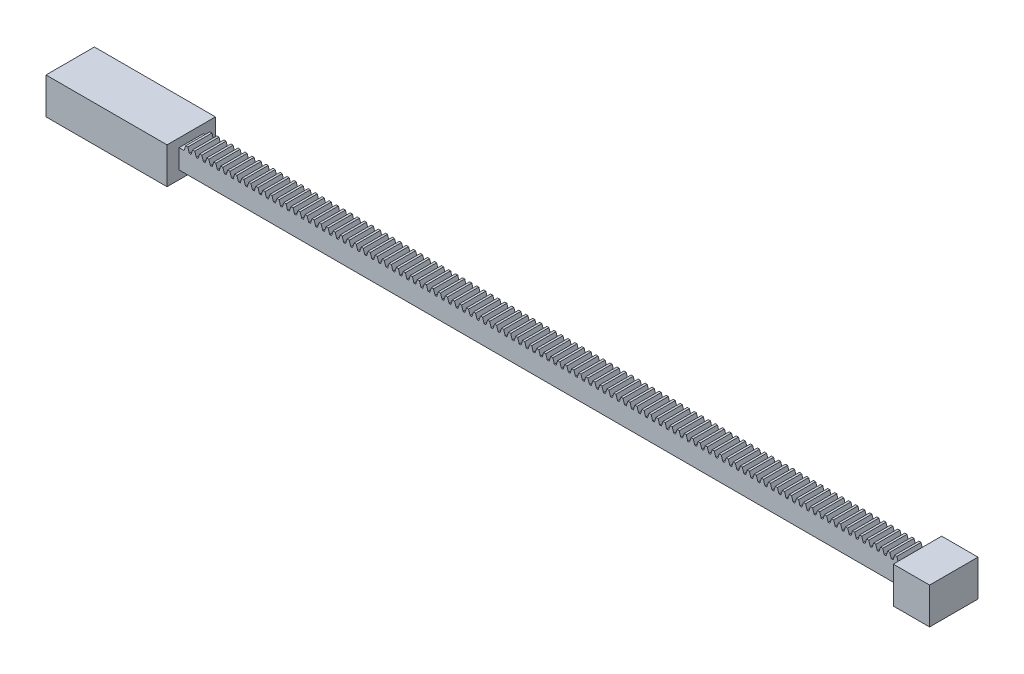
SolidWorks part; units mm, degrees
ref_plane "Front Plane" through (0, 0, 0) normal (0, 0, 1) x (1, 0, 0)
ref_plane "Top Plane" through (0, 0, 0) normal (0, 1, 0) x (1, 0, 0)
ref_plane "Right Plane" through (0, 0, 0) normal (1, 0, 0) x (0, 0, -1)
sketch "Sketch1" plane through (0, 0, 0) normal (0, 0, 1) x (1, 0, 0)
  line L0 (147.8394, 4) -> (148.4797, 6)
  line L1 (-150, 4) -> (150, 4)
  line L2 (-150, 4) -> (-150, -4)
  line L3 (-150, -4) -> (150, -4)
  line L4 (150, 4) -> (150, -4)
  line L5 (-150, 4) -> (150, -4) construction
  line L6 (-150, -4) -> (150, 4) construction
  line L7 (148.4797, 6) -> (149.3597, 6)
  line L8 (149.3597, 6) -> (150, 4)
  line L9 (144.9394, 4) -> (145.5797, 6)
  line L10 (145.5797, 6) -> (146.4597, 6)
  line L11 (146.4597, 6) -> (147.1, 4)
  line L12 (142.0394, 4) -> (142.6797, 6)
  line L13 (142.6797, 6) -> (143.5597, 6)
  line L14 (143.5597, 6) -> (144.2, 4)
  line L15 (139.1394, 4) -> (139.7797, 6)
  line L16 (139.7797, 6) -> (140.6597, 6)
  line L17 (140.6597, 6) -> (141.3, 4)
  line L18 (136.2394, 4) -> (136.8797, 6)
  line L19 (136.8797, 6) -> (137.7597, 6)
  line L20 (137.7597, 6) -> (138.4, 4)
  line L21 (133.3394, 4) -> (133.9797, 6)
  line L22 (133.9797, 6) -> (134.8597, 6)
  line L23 (134.8597, 6) -> (135.5, 4)
  line L24 (130.4394, 4) -> (131.0797, 6)
  line L25 (131.0797, 6) -> (131.9597, 6)
  line L26 (131.9597, 6) -> (132.6, 4)
  line L27 (127.5394, 4) -> (128.1797, 6)
  line L28 (128.1797, 6) -> (129.0597, 6)
  line L29 (129.0597, 6) -> (129.7, 4)
  line L30 (124.6394, 4) -> (125.2797, 6)
  line L31 (125.2797, 6) -> (126.1597, 6)
  line L32 (126.1597, 6) -> (126.8, 4)
  line L33 (121.7394, 4) -> (122.3797, 6)
  line L34 (122.3797, 6) -> (123.2597, 6)
  line L35 (123.2597, 6) -> (123.9, 4)
  line L36 (118.8394, 4) -> (119.4797, 6)
  line L37 (119.4797, 6) -> (120.3597, 6)
  line L38 (120.3597, 6) -> (121, 4)
  line L39 (115.9394, 4) -> (116.5797, 6)
  line L40 (116.5797, 6) -> (117.4597, 6)
  line L41 (117.4597, 6) -> (118.1, 4)
  line L42 (113.0394, 4) -> (113.6797, 6)
  line L43 (113.6797, 6) -> (114.5597, 6)
  line L44 (114.5597, 6) -> (115.2, 4)
  line L45 (110.1394, 4) -> (110.7797, 6)
  line L46 (110.7797, 6) -> (111.6597, 6)
  line L47 (111.6597, 6) -> (112.3, 4)
  line L48 (107.2394, 4) -> (107.8797, 6)
  line L49 (107.8797, 6) -> (108.7597, 6)
  line L50 (108.7597, 6) -> (109.4, 4)
  line L51 (104.3394, 4) -> (104.9797, 6)
  line L52 (104.9797, 6) -> (105.8597, 6)
  line L53 (105.8597, 6) -> (106.5, 4)
  line L54 (101.4394, 4) -> (102.0797, 6)
  line L55 (102.0797, 6) -> (102.9597, 6)
  line L56 (102.9597, 6) -> (103.6, 4)
  line L57 (98.5394, 4) -> (99.1797, 6)
  line L58 (99.1797, 6) -> (100.0597, 6)
  line L59 (100.0597, 6) -> (100.7, 4)
  line L60 (95.6394, 4) -> (96.2797, 6)
  line L61 (96.2797, 6) -> (97.1597, 6)
  line L62 (97.1597, 6) -> (97.8, 4)
  line L63 (92.7394, 4) -> (93.3797, 6)
  line L64 (93.3797, 6) -> (94.2597, 6)
  line L65 (94.2597, 6) -> (94.9, 4)
  line L66 (89.8394, 4) -> (90.4797, 6)
  line L67 (90.4797, 6) -> (91.3597, 6)
  line L68 (91.3597, 6) -> (92, 4)
  line L69 (86.9394, 4) -> (87.5797, 6)
  line L70 (87.5797, 6) -> (88.4597, 6)
  line L71 (88.4597, 6) -> (89.1, 4)
  line L72 (84.0394, 4) -> (84.6797, 6)
  line L73 (84.6797, 6) -> (85.5597, 6)
  line L74 (85.5597, 6) -> (86.2, 4)
  line L75 (81.1394, 4) -> (81.7797, 6)
  line L76 (81.7797, 6) -> (82.6597, 6)
  line L77 (82.6597, 6) -> (83.3, 4)
  line L78 (78.2394, 4) -> (78.8797, 6)
  line L79 (78.8797, 6) -> (79.7597, 6)
  line L80 (79.7597, 6) -> (80.4, 4)
  line L81 (75.3394, 4) -> (75.9797, 6)
  line L82 (75.9797, 6) -> (76.8597, 6)
  line L83 (76.8597, 6) -> (77.5, 4)
  line L84 (72.4394, 4) -> (73.0797, 6)
  line L85 (73.0797, 6) -> (73.9597, 6)
  line L86 (73.9597, 6) -> (74.6, 4)
  line L87 (69.5394, 4) -> (70.1797, 6)
  line L88 (70.1797, 6) -> (71.0597, 6)
  line L89 (71.0597, 6) -> (71.7, 4)
  line L90 (66.6394, 4) -> (67.2797, 6)
  line L91 (67.2797, 6) -> (68.1597, 6)
  line L92 (68.1597, 6) -> (68.8, 4)
  line L93 (63.7394, 4) -> (64.3797, 6)
  line L94 (64.3797, 6) -> (65.2597, 6)
  line L95 (65.2597, 6) -> (65.9, 4)
  line L96 (60.8394, 4) -> (61.4797, 6)
  line L97 (61.4797, 6) -> (62.3597, 6)
  line L98 (62.3597, 6) -> (63, 4)
  line L99 (57.9394, 4) -> (58.5797, 6)
  line L100 (58.5797, 6) -> (59.4597, 6)
  line L101 (59.4597, 6) -> (60.1, 4)
  line L102 (55.0394, 4) -> (55.6797, 6)
  line L103 (55.6797, 6) -> (56.5597, 6)
  line L104 (56.5597, 6) -> (57.2, 4)
  line L105 (52.1394, 4) -> (52.7797, 6)
  line L106 (52.7797, 6) -> (53.6597, 6)
  line L107 (53.6597, 6) -> (54.3, 4)
  line L108 (49.2394, 4) -> (49.8797, 6)
  line L109 (49.8797, 6) -> (50.7597, 6)
  line L110 (50.7597, 6) -> (51.4, 4)
  line L111 (46.3394, 4) -> (46.9797, 6)
  line L112 (46.9797, 6) -> (47.8597, 6)
  line L113 (47.8597, 6) -> (48.5, 4)
  line L114 (43.4394, 4) -> (44.0797, 6)
  line L115 (44.0797, 6) -> (44.9597, 6)
  line L116 (44.9597, 6) -> (45.6, 4)
  line L117 (40.5394, 4) -> (41.1797, 6)
  line L118 (41.1797, 6) -> (42.0597, 6)
  line L119 (42.0597, 6) -> (42.7, 4)
  line L120 (37.6394, 4) -> (38.2797, 6)
  line L121 (38.2797, 6) -> (39.1597, 6)
  line L122 (39.1597, 6) -> (39.8, 4)
  line L123 (34.7394, 4) -> (35.3797, 6)
  line L124 (35.3797, 6) -> (36.2597, 6)
  line L125 (36.2597, 6) -> (36.9, 4)
  line L126 (31.8394, 4) -> (32.4797, 6)
  line L127 (32.4797, 6) -> (33.3597, 6)
  line L128 (33.3597, 6) -> (34, 4)
  line L129 (28.9394, 4) -> (29.5797, 6)
  line L130 (29.5797, 6) -> (30.4597, 6)
  line L131 (30.4597, 6) -> (31.1, 4)
  line L132 (26.0394, 4) -> (26.6797, 6)
  line L133 (26.6797, 6) -> (27.5597, 6)
  line L134 (27.5597, 6) -> (28.2, 4)
  line L135 (23.1394, 4) -> (23.7797, 6)
  line L136 (23.7797, 6) -> (24.6597, 6)
  line L137 (24.6597, 6) -> (25.3, 4)
  line L138 (20.2394, 4) -> (20.8797, 6)
  line L139 (20.8797, 6) -> (21.7597, 6)
  line L140 (21.7597, 6) -> (22.4, 4)
  line L141 (17.3394, 4) -> (17.9797, 6)
  line L142 (17.9797, 6) -> (18.8597, 6)
  line L143 (18.8597, 6) -> (19.5, 4)
  line L144 (14.4394, 4) -> (15.0797, 6)
  line L145 (15.0797, 6) -> (15.9597, 6)
  line L146 (15.9597, 6) -> (16.6, 4)
  line L147 (11.5394, 4) -> (12.1797, 6)
  line L148 (12.1797, 6) -> (13.0597, 6)
  line L149 (13.0597, 6) -> (13.7, 4)
  line L150 (8.6394, 4) -> (9.2797, 6)
  line L151 (9.2797, 6) -> (10.1597, 6)
  line L152 (10.1597, 6) -> (10.8, 4)
  line L153 (5.7394, 4) -> (6.3797, 6)
  line L154 (6.3797, 6) -> (7.2597, 6)
  line L155 (7.2597, 6) -> (7.9, 4)
  line L156 (2.8394, 4) -> (3.4797, 6)
  line L157 (3.4797, 6) -> (4.3597, 6)
  line L158 (4.3597, 6) -> (5, 4)
  line L159 (-0.0606, 4) -> (0.5797, 6)
  line L160 (0.5797, 6) -> (1.4597, 6)
  line L161 (1.4597, 6) -> (2.1, 4)
  line L162 (-2.9606, 4) -> (-2.3203, 6)
  line L163 (-2.3203, 6) -> (-1.4403, 6)
  line L164 (-1.4403, 6) -> (-0.8, 4)
  line L165 (-5.8606, 4) -> (-5.2203, 6)
  line L166 (-5.2203, 6) -> (-4.3403, 6)
  line L167 (-4.3403, 6) -> (-3.7, 4)
  line L168 (-8.7606, 4) -> (-8.1203, 6)
  line L169 (-8.1203, 6) -> (-7.2403, 6)
  line L170 (-7.2403, 6) -> (-6.6, 4)
  line L171 (-11.6606, 4) -> (-11.0203, 6)
  line L172 (-11.0203, 6) -> (-10.1403, 6)
  line L173 (-10.1403, 6) -> (-9.5, 4)
  line L174 (-14.5606, 4) -> (-13.9203, 6)
  line L175 (-13.9203, 6) -> (-13.0403, 6)
  line L176 (-13.0403, 6) -> (-12.4, 4)
  line L177 (-17.4606, 4) -> (-16.8203, 6)
  line L178 (-16.8203, 6) -> (-15.9403, 6)
  line L179 (-15.9403, 6) -> (-15.3, 4)
  line L180 (-20.3606, 4) -> (-19.7203, 6)
  line L181 (-19.7203, 6) -> (-18.8403, 6)
  line L182 (-18.8403, 6) -> (-18.2, 4)
  line L183 (-23.2606, 4) -> (-22.6203, 6)
  line L184 (-22.6203, 6) -> (-21.7403, 6)
  line L185 (-21.7403, 6) -> (-21.1, 4)
  line L186 (-26.1606, 4) -> (-25.5203, 6)
  line L187 (-25.5203, 6) -> (-24.6403, 6)
  line L188 (-24.6403, 6) -> (-24, 4)
  line L189 (-29.0606, 4) -> (-28.4203, 6)
  line L190 (-28.4203, 6) -> (-27.5403, 6)
  line L191 (-27.5403, 6) -> (-26.9, 4)
  line L192 (-31.9606, 4) -> (-31.3203, 6)
  line L193 (-31.3203, 6) -> (-30.4403, 6)
  line L194 (-30.4403, 6) -> (-29.8, 4)
  line L195 (-34.8606, 4) -> (-34.2203, 6)
  line L196 (-34.2203, 6) -> (-33.3403, 6)
  line L197 (-33.3403, 6) -> (-32.7, 4)
  line L198 (-37.7606, 4) -> (-37.1203, 6)
  line L199 (-37.1203, 6) -> (-36.2403, 6)
  line L200 (-36.2403, 6) -> (-35.6, 4)
  line L201 (-40.6606, 4) -> (-40.0203, 6)
  line L202 (-40.0203, 6) -> (-39.1403, 6)
  line L203 (-39.1403, 6) -> (-38.5, 4)
  line L204 (-43.5606, 4) -> (-42.9203, 6)
  line L205 (-42.9203, 6) -> (-42.0403, 6)
  line L206 (-42.0403, 6) -> (-41.4, 4)
  line L207 (-46.4606, 4) -> (-45.8203, 6)
  line L208 (-45.8203, 6) -> (-44.9403, 6)
  line L209 (-44.9403, 6) -> (-44.3, 4)
  line L210 (-49.3606, 4) -> (-48.7203, 6)
  line L211 (-48.7203, 6) -> (-47.8403, 6)
  line L212 (-47.8403, 6) -> (-47.2, 4)
  line L213 (-52.2606, 4) -> (-51.6203, 6)
  line L214 (-51.6203, 6) -> (-50.7403, 6)
  line L215 (-50.7403, 6) -> (-50.1, 4)
  line L216 (-55.1606, 4) -> (-54.5203, 6)
  line L217 (-54.5203, 6) -> (-53.6403, 6)
  line L218 (-53.6403, 6) -> (-53, 4)
  line L219 (-58.0606, 4) -> (-57.4203, 6)
  line L220 (-57.4203, 6) -> (-56.5403, 6)
  line L221 (-56.5403, 6) -> (-55.9, 4)
  line L222 (-60.9606, 4) -> (-60.3203, 6)
  line L223 (-60.3203, 6) -> (-59.4403, 6)
  line L224 (-59.4403, 6) -> (-58.8, 4)
  line L225 (-63.8606, 4) -> (-63.2203, 6)
  line L226 (-63.2203, 6) -> (-62.3403, 6)
  line L227 (-62.3403, 6) -> (-61.7, 4)
  line L228 (-66.7606, 4) -> (-66.1203, 6)
  line L229 (-66.1203, 6) -> (-65.2403, 6)
  line L230 (-65.2403, 6) -> (-64.6, 4)
  line L231 (-69.6606, 4) -> (-69.0203, 6)
  line L232 (-69.0203, 6) -> (-68.1403, 6)
  line L233 (-68.1403, 6) -> (-67.5, 4)
  line L234 (-72.5606, 4) -> (-71.9203, 6)
  line L235 (-71.9203, 6) -> (-71.0403, 6)
  line L236 (-71.0403, 6) -> (-70.4, 4)
  line L237 (-75.4606, 4) -> (-74.8203, 6)
  line L238 (-74.8203, 6) -> (-73.9403, 6)
  line L239 (-73.9403, 6) -> (-73.3, 4)
  line L240 (-78.3606, 4) -> (-77.7203, 6)
  line L241 (-77.7203, 6) -> (-76.8403, 6)
  line L242 (-76.8403, 6) -> (-76.2, 4)
  line L243 (-81.2606, 4) -> (-80.6203, 6)
  line L244 (-80.6203, 6) -> (-79.7403, 6)
  line L245 (-79.7403, 6) -> (-79.1, 4)
  line L246 (-84.1606, 4) -> (-83.5203, 6)
  line L247 (-83.5203, 6) -> (-82.6403, 6)
  line L248 (-82.6403, 6) -> (-82, 4)
  line L249 (-87.0606, 4) -> (-86.4203, 6)
  line L250 (-86.4203, 6) -> (-85.5403, 6)
  line L251 (-85.5403, 6) -> (-84.9, 4)
  line L252 (-89.9606, 4) -> (-89.3203, 6)
  line L253 (-89.3203, 6) -> (-88.4403, 6)
  line L254 (-88.4403, 6) -> (-87.8, 4)
  line L255 (-92.8606, 4) -> (-92.2203, 6)
  line L256 (-92.2203, 6) -> (-91.3403, 6)
  line L257 (-91.3403, 6) -> (-90.7, 4)
  line L258 (-95.7606, 4) -> (-95.1203, 6)
  line L259 (-95.1203, 6) -> (-94.2403, 6)
  line L260 (-94.2403, 6) -> (-93.6, 4)
  line L261 (-98.6606, 4) -> (-98.0203, 6)
  line L262 (-98.0203, 6) -> (-97.1403, 6)
  line L263 (-97.1403, 6) -> (-96.5, 4)
  line L264 (-101.5606, 4) -> (-100.9203, 6)
  line L265 (-100.9203, 6) -> (-100.0403, 6)
  line L266 (-100.0403, 6) -> (-99.4, 4)
  line L267 (-104.4606, 4) -> (-103.8203, 6)
  line L268 (-103.8203, 6) -> (-102.9403, 6)
  line L269 (-102.9403, 6) -> (-102.3, 4)
  line L270 (-107.3606, 4) -> (-106.7203, 6)
  line L271 (-106.7203, 6) -> (-105.8403, 6)
  line L272 (-105.8403, 6) -> (-105.2, 4)
  line L273 (-110.2606, 4) -> (-109.6203, 6)
  line L274 (-109.6203, 6) -> (-108.7403, 6)
  line L275 (-108.7403, 6) -> (-108.1, 4)
  line L276 (-113.1606, 4) -> (-112.5203, 6)
  line L277 (-112.5203, 6) -> (-111.6403, 6)
  line L278 (-111.6403, 6) -> (-111, 4)
  line L279 (-116.0606, 4) -> (-115.4203, 6)
  line L280 (-115.4203, 6) -> (-114.5403, 6)
  line L281 (-114.5403, 6) -> (-113.9, 4)
  line L282 (-118.9606, 4) -> (-118.3203, 6)
  line L283 (-118.3203, 6) -> (-117.4403, 6)
  line L284 (-117.4403, 6) -> (-116.8, 4)
  line L285 (-121.8606, 4) -> (-121.2203, 6)
  line L286 (-121.2203, 6) -> (-120.3403, 6)
  line L287 (-120.3403, 6) -> (-119.7, 4)
  line L288 (-124.7606, 4) -> (-124.1203, 6)
  line L289 (-124.1203, 6) -> (-123.2403, 6)
  line L290 (-123.2403, 6) -> (-122.6, 4)
  line L291 (-127.6606, 4) -> (-127.0203, 6)
  line L292 (-127.0203, 6) -> (-126.1403, 6)
  line L293 (-126.1403, 6) -> (-125.5, 4)
  line L294 (-130.5606, 4) -> (-129.9203, 6)
  line L295 (-129.9203, 6) -> (-129.0403, 6)
  line L296 (-129.0403, 6) -> (-128.4, 4)
  line L297 (-133.4606, 4) -> (-132.8203, 6)
  line L298 (-132.8203, 6) -> (-131.9403, 6)
  line L299 (-131.9403, 6) -> (-131.3, 4)
  line L300 (-136.3606, 4) -> (-135.7203, 6)
  line L301 (-135.7203, 6) -> (-134.8403, 6)
  line L302 (-134.8403, 6) -> (-134.2, 4)
  line L303 (-139.2606, 4) -> (-138.6203, 6)
  line L304 (-138.6203, 6) -> (-137.7403, 6)
  line L305 (-137.7403, 6) -> (-137.1, 4)
  line L306 (-142.1606, 4) -> (-141.5203, 6)
  line L307 (-141.5203, 6) -> (-140.6403, 6)
  line L308 (-140.6403, 6) -> (-140, 4)
  line L309 (-145.0606, 4) -> (-144.4203, 6)
  line L310 (-144.4203, 6) -> (-143.5403, 6)
  line L311 (-143.5403, 6) -> (-142.9, 4)
  line L312 (-147.9606, 4) -> (-147.3203, 6)
  line L313 (-147.3203, 6) -> (-146.4403, 6)
  line L314 (-146.4403, 6) -> (-145.8, 4)
  point P0 (0, 0)
  dimension "D1" = 8
  dimension "D2" = 300
  dimension "D3" = 0.88
  dimension "D4" = 2
  dimension "D5" = 2.1
  dimension "D6" = 2.1606
  dimension "D7" = 103
extrude "Boss-Extrude1" add sketch "Sketch1" along normal blind 10 contours L4 L1 region at (0, 0, 0)
sketch "Sketch2" plane through (0, 0, 10) normal (0, 0, 1) x (1, 0, 0)
  line L3 (147.8394, 4) -> (148.4797, 6)
  line L4 (150, -4) -> (150, 4)
  line L5 (150, 4) -> (-150, 4)
  line L6 (-150, 4) -> (-150, -4)
  line L7 (-150, -4) -> (150, -4)
  line L9 (150, 4) -> (147.8394, 4)
  line L12 (148.4797, 6) -> (149.3597, 6)
  line L13 (149.3597, 6) -> (150, 4)
  dimension "D1" = 0
extrude "Boss-Extrude2" add sketch "Sketch2" against normal blind 10
pattern_linear "LPattern1" count 103 spacing 2.9 along (-1, 0, 0) of "Boss-Extrude2"
sketch "Sketch3" plane through (150, 0, 0) normal (1, 0, 0) x (0, 0, -1)
  line L0 (-10, -4) -> (0, -4) construction
  line L1 (-15, 7.5) -> (5, 7.5)
  line L2 (-15, 7.5) -> (-15, -7.5)
  line L3 (-15, -7.5) -> (5, -7.5)
  line L4 (5, 7.5) -> (5, -7.5)
  line L5 (-15, 7.5) -> (5, -7.5) construction
  line L6 (-15, -7.5) -> (5, 7.5) construction
  point P0 (-5, 0)
  point P8 (-5, -4)
  dimension "D1" = 20
  dimension "D2" = 15
extrude "Boss-Extrude3" add sketch "Sketch3" along normal blind 15
sketch "Sketch4" plane through (-150, 0, 0) normal (-1, 0, 0) x (0, 0, 1)
  line L0 (-5, -7.5) -> (-5, 7.5) construction
  line L1 (-5, -7.5) -> (-5, 7.5)
  line L2 (15, -7.5) -> (-5, -7.5) construction
  line L3 (15, 7.5) -> (15, -7.5) construction
  line L4 (-5, 7.5) -> (15, 7.5) construction
  line L5 (15, -7.5) -> (-5, -7.5)
  line L6 (15, 7.5) -> (15, -7.5)
  line L7 (-5, 7.5) -> (15, 7.5)
extrude "Boss-Extrude4" add sketch "Sketch4" along normal blind 50
sketch "Sketch5" plane through (-200, 0, 0) normal (-1, 0, 0) x (0, 0, 1)
  line L0 (-7, -16.5) -> (17, -16.5) construction
  line L2 (-5, -7.5) -> (15, -7.5) construction
  circle A0 centre (5, -16.5) radius 9
  circle A1 centre (5, -16.5) radius 12
  dimension "D1" = 3
extrude "Boss-Extrude6" [suppressed] add sketch "Sketch5" against normal blind 30
